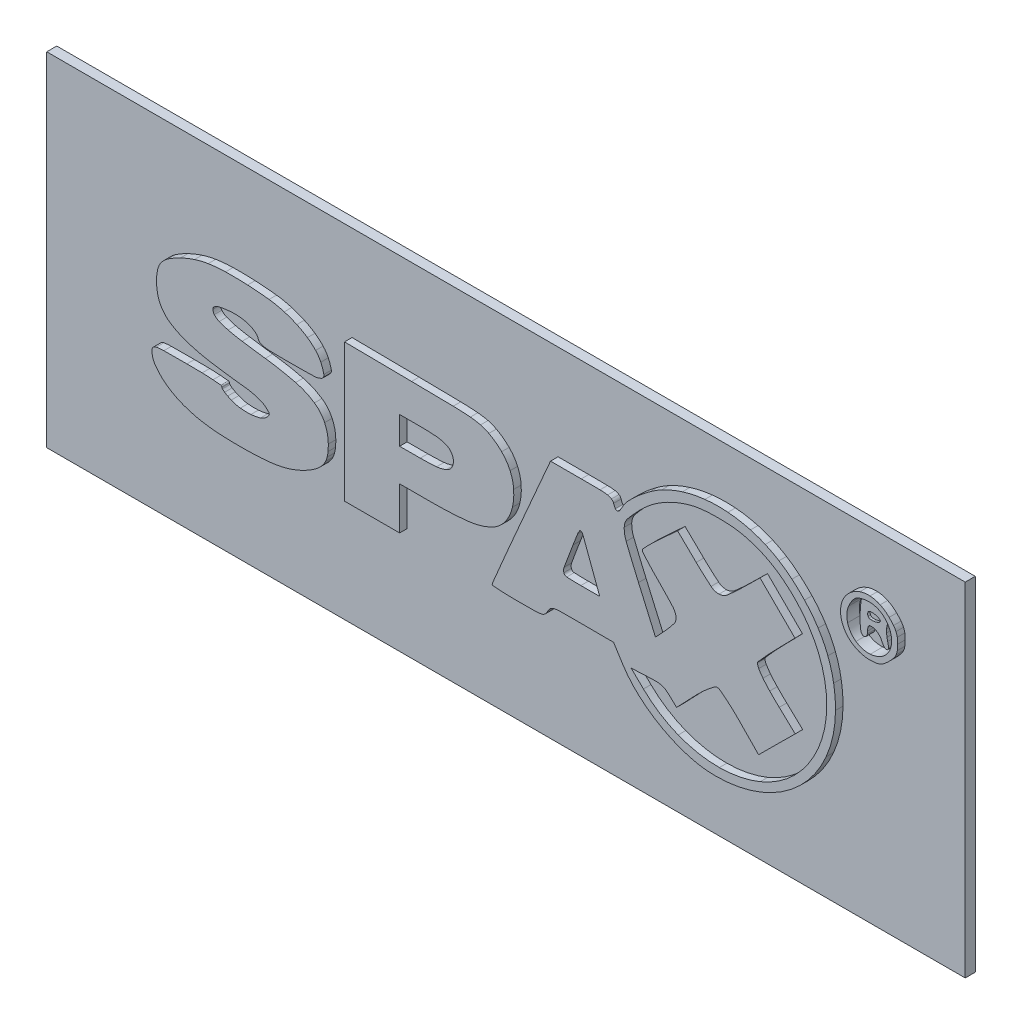
SolidWorks part; units mm, degrees
ref_plane "Front Plane" through (0, 0, 0) normal (0, 0, 1) x (1, 0, 0)
ref_plane "Top Plane" through (0, 0, 0) normal (0, 1, 0) x (1, 0, 0)
ref_plane "Right Plane" through (0, 0, 0) normal (1, 0, 0) x (0, 0, -1)
sketch "Model" plane through (0, 0, 0) normal (0, 0, 1) x (1, 0, 0)
  line L0 (0, 68.5) -> (0, 0)
  line L1 (0, 0) -> (183.5, 0)
  line L2 (183.5, 0) -> (367, 0)
  line L3 (367, 0) -> (367, 68.5)
  line L4 (367, 68.5) -> (367, 137)
  line L5 (367, 137) -> (183.5, 137)
  line L6 (183.5, 137) -> (0, 137)
  line L7 (0, 137) -> (0, 68.5)
  line L8 (233, 43.3516) -> (229.5, 48.9039)
  line L9 (229.5, 48.9039) -> (216.9105, 48.9519)
  line L10 (181.1093, 45.2449) -> (184.4205, 53.0742)
  line L11 (188.1802, 61.882) -> (192.6443, 72.2052)
  line L12 (192.6443, 72.2052) -> (204.2887, 99)
  line L13 (204.2887, 99) -> (216.5769, 99)
  line L14 (157.3185, 61) -> (144, 61)
  line L15 (144, 61) -> (144, 52.5)
  line L16 (144, 52.5) -> (144, 44)
  line L17 (144, 44) -> (133, 44)
  line L18 (133, 44) -> (122, 44)
  line L19 (122, 44) -> (122, 71.5596)
  line L20 (122, 71.5596) -> (122, 99.1193)
  line L21 (122, 99.1193) -> (148.75, 98.8096)
  line L22 (239.4571, 74.5616) -> (246.2264, 59.0751)
  line L23 (246.2264, 59.0751) -> (250.11, 63.2399)
  line L24 (251.2781, 96.8241) -> (255.0562, 100.2835)
  line L25 (255.0562, 100.2835) -> (262.5002, 93.0655)
  line L26 (281.25, 93.8265) -> (288, 100.4464)
  line L27 (288, 100.4464) -> (294.9777, 93.5221)
  line L28 (294.9777, 93.5221) -> (301.9555, 86.5978)
  line L29 (301.9555, 86.5978) -> (294.4777, 78.9138)
  line L30 (295.6641, 59.4982) -> (302.0467, 53.4963)
  line L31 (302.0467, 53.4963) -> (294.7339, 46.2324)
  line L32 (294.7339, 46.2324) -> (287.4212, 38.9684)
  line L33 (287.4212, 38.9684) -> (280.0813, 46.4842)
  line L34 (261.8493, 46.4788) -> (254.6537, 38.9576)
  line L35 (254.6537, 38.9576) -> (251.9685, 41.5302)
  line L36 (242.8916, 43.8014) -> (236.5, 43.5)
  line L37 (236.5, 43.5) -> (241.4223, 38.7189)
  line L38 (216.4075, 62) -> (223.9497, 62)
  line L39 (223.9497, 62) -> (221.0637, 69.75)
  line L40 (221.0637, 69.75) -> (219.89, 72.8972)
  line L41 (219.89, 72.8972) -> (218.7502, 75.9447)
  line L42 (218.7502, 75.9447) -> (217.7735, 78.5484)
  line L43 (217.7735, 78.5484) -> (217.2407, 79.9555)
  line L44 (144, 79.5) -> (144, 74)
  line L45 (144, 74) -> (152.25, 74.0147)
  line L46 (152.25, 84.9853) -> (144, 85)
  line L47 (144, 85) -> (144, 79.5)
  arc A0 (290.0898, 113.0599) -> (284.1892, 115.1571) centre (272.3977, 72.6332) ccw
  arc A1 (295.5669, 110.1672) -> (290.0898, 113.0599) centre (273.152, 74.3567) ccw
  arc A2 (300.7497, 106.3903) -> (295.5669, 110.1672) centre (271.4155, 71.5822) ccw
  arc A3 (305.7714, 101.6482) -> (300.7497, 106.3903) centre (261.3422, 59.629) ccw
  arc A4 (311.219, 94.6965) -> (305.7714, 101.6482) centre (271.165, 68.919) ccw
  arc A5 (315.1092, 87.0501) -> (311.219, 94.6965) centre (275.518, 71.7204) ccw
  arc A6 (317.4144, 78.6997) -> (315.1092, 87.0501) centre (274.6776, 71.395) ccw
  arc A7 (318.1578, 69.6584) -> (317.4144, 78.6997) centre (266.1058, 69.9299) ccw
  arc A8 (314.4227, 51.7702) -> (318.1578, 69.6584) centre (272.309, 69.8976) ccw
  arc A9 (303.9858, 36.6225) -> (314.4227, 51.7702) centre (271.2262, 70.3638) ccw
  arc A10 (288.4274, 26.5204) -> (303.9858, 36.6225) centre (270.5991, 71.0097) ccw
  arc A11 (270.1135, 23.0119) -> (288.4274, 26.5204) centre (270.2393, 71.9074) ccw
  arc A12 (259.627, 24.499) -> (270.1135, 23.0119) centre (270.2123, 61.4243) ccw
  arc A13 (249.0758, 28.8394) -> (259.627, 24.499) centre (273.8083, 73.9683) ccw
  arc A14 (239.7791, 35.376) -> (249.0758, 28.8394) centre (273.6252, 73.6343) ccw
  arc A15 (233, 43.3516) -> (239.7791, 35.376) centre (264.2776, 63.068) ccw
  arc A16 (216.9105, 48.9519) -> (208.649, 48.9371) centre (214.104, -686.3237) ccw
  arc A17 (208.649, 48.9371) -> (205.7901, 48.6731) centre (208.7749, 31.961) ccw
  arc A18 (205.7901, 48.6731) -> (204.2704, 47.9506) centre (206.3507, 45.5345) ccw
  arc A19 (204.2704, 47.9506) -> (203.182, 46.5) centre (207.0283, 44.7475) ccw
  arc A20 (202.1569, 45.0625) -> (203.182, 46.5) centre (198.9709, 48.4187) ccw
  arc A21 (200.7801, 44.3365) -> (202.1569, 45.0625) centre (200.1774, 47.1477) ccw
  arc A22 (198.2741, 44.0515) -> (200.7801, 44.3365) centre (198.0774, 56.9424) ccw
  arc A23 (191.5214, 44) -> (198.2741, 44.0515) centre (191.5213, 486.7578) ccw
  arc A24 (187.4872, 44.0507) -> (191.5214, 44) centre (191.5215, 204.5428) ccw
  arc A25 (184.0907, 44.2071) -> (187.4872, 44.0507) centre (189.5322, 125.3989) ccw
  arc A26 (181.2609, 44.4213) -> (184.0907, 44.2071) centre (195.0833, 208.2248) ccw
  arc A27 (181, 44.7052) -> (181.2609, 44.4213) centre (181.2848, 44.7052) ccw
  arc A28 (181.1093, 45.2449) -> (181, 44.7052) centre (182.3871, 44.7052) ccw
  arc A29 (188.1802, 61.882) -> (184.4205, 53.0742) centre (1701.7504, -589.4075) ccw
  arc A30 (224.0574, 98.9504) -> (216.5769, 99) centre (216.5772, -465.3246) ccw
  arc A31 (227.0962, 98.6964) -> (224.0574, 98.9504) centre (223.7691, 77.198) ccw
  arc A32 (228.6554, 98.1043) -> (227.0962, 98.6964) centre (226.4826, 94.7315) ccw
  arc A33 (229.5, 97) -> (228.6554, 98.1043) centre (227.5441, 96.3792) ccw
  arc A34 (229.5, 97) -> (230.1856, 95.4829) centre (236.2898, 99.155) ccw
  arc A35 (230.1856, 95.4829) -> (230.9729, 95.1226) centre (230.8426, 95.8781) ccw
  arc A36 (230.9729, 95.1226) -> (231.889, 95.7046) centre (230.7333, 96.5116) ccw
  arc A37 (231.889, 95.7046) -> (233.0611, 97.6142) centre (216.3408, 106.5627) ccw
  arc A38 (235.298, 100.6952) -> (233.0611, 97.6142) centre (245.3882, 91.017) ccw
  arc A39 (239.3724, 104.58) -> (235.298, 100.6952) centre (280.8087, 57.0423) ccw
  arc A40 (244.1225, 108.3569) -> (239.3724, 104.58) centre (283.5278, 53.9228) ccw
  arc A41 (248.6856, 111.2333) -> (244.1225, 108.3569) centre (268.7919, 74.2789) ccw
  arc A42 (256.9986, 114.7387) -> (248.6856, 111.2333) centre (270.4447, 71.2412) ccw
  arc A43 (265.9667, 116.6027) -> (256.9986, 114.7387) centre (271.2779, 68.5457) ccw
  arc A44 (275.1724, 116.7474) -> (265.9667, 116.6027) centre (271.3338, 68.0404) ccw
  arc A45 (284.1892, 115.1571) -> (275.1724, 116.7474) centre (271.4171, 69.0968) ccw
  arc A46 (341.3538, 110.6565) -> (339.6, 112.6) centre (321.5322, 94.5323) ccw
  arc A47 (342.3452, 109.0459) -> (341.3538, 110.6565) centre (335.7431, 106.0923) ccw
  arc A48 (342.8416, 107.3117) -> (342.3452, 109.0459) centre (336.5241, 106.4418) ccw
  arc A49 (343, 105) -> (342.8416, 107.3117) centre (326.0537, 105) ccw
  arc A50 (342.8416, 102.6883) -> (343, 105) centre (326.0537, 105) ccw
  arc A51 (342.3452, 100.9541) -> (342.8416, 102.6883) centre (336.5241, 103.5582) ccw
  arc A52 (341.3538, 99.3435) -> (342.3452, 100.9541) centre (335.7431, 103.9077) ccw
  arc A53 (339.6, 97.4) -> (341.3538, 99.3435) centre (321.5322, 115.4677) ccw
  arc A54 (337.6196, 95.6125) -> (339.6, 97.4) centre (321.1442, 115.8558) ccw
  arc A55 (336.0024, 94.6307) -> (337.6196, 95.6125) centre (333.2651, 100.9629) ccw
  arc A56 (334.2232, 94.1496) -> (336.0024, 94.6307) centre (333.4533, 100.5274) ccw
  arc A57 (331.7349, 94) -> (334.2232, 94.1496) centre (331.7348, 114.764) ccw
  arc A58 (325.1323, 95.9651) -> (331.7349, 94) centre (331.7348, 106.0742) ccw
  arc A59 (320.8895, 101.1799) -> (325.1323, 95.9651) centre (331.1722, 105.2127) ccw
  arc A60 (320.5156, 107.7805) -> (320.8895, 101.1799) centre (330.7564, 105.0496) ccw
  arc A61 (324.1107, 113.4397) -> (320.5156, 107.7805) centre (331.2903, 104.9073) ccw
  arc A62 (327.8418, 115.5802) -> (324.1107, 113.4397) centre (331.9031, 104.179) ccw
  arc A63 (331.9489, 116.1759) -> (327.8418, 115.5802) centre (331.3784, 105.6521) ccw
  arc A64 (336.0082, 115.1399) -> (331.9489, 116.1759) centre (331.3658, 105.4204) ccw
  arc A65 (339.6, 112.6) -> (336.0082, 115.1399) centre (330.4016, 103.4016) ccw
  arc A66 (102.9313, 95.5692) -> (97.8951, 97.4576) centre (86.3036, 58.8849) ccw
  arc A67 (107.1665, 93.1697) -> (102.9313, 95.5692) centre (91.7398, 70.8782) ccw
  arc A68 (110.4184, 90.3864) -> (107.1665, 93.1697) centre (95.2683, 75.9768) ccw
  arc A69 (112.506, 87.3462) -> (110.4184, 90.3864) centre (101.9607, 82.3422) ccw
  arc A70 (113.704, 83.7167) -> (112.506, 87.3462) centre (98.5735, 80.7348) ccw
  arc A71 (112.8606, 81.9404) -> (113.704, 83.7167) centre (112.084, 83.3975) ccw
  arc A72 (109.8322, 81.1361) -> (112.8606, 81.9404) centre (109.6297, 88.0023) ccw
  arc A73 (100.5988, 81) -> (109.8322, 81.1361) centre (100.5988, 394.2614) ccw
  arc A74 (93.1747, 81.0507) -> (100.5988, 81) centre (100.5983, 624.6647) ccw
  arc A75 (90.0154, 81.3) -> (93.1747, 81.0507) centre (93.5073, 105.4064) ccw
  arc A76 (88.3759, 81.8579) -> (90.0154, 81.3) centre (90.6934, 85.9807) ccw
  arc A77 (87.5341, 82.8925) -> (88.3759, 81.8579) centre (89.2666, 83.4423) ccw
  arc A78 (87.5341, 82.8925) -> (86.2044, 84.7323) centre (84.0792, 81.7959) ccw
  arc A79 (86.2044, 84.7323) -> (83.5728, 86.0836) centre (80.4813, 76.8247) ccw
  arc A80 (83.5728, 86.0836) -> (80.0127, 86.8047) centre (78.8619, 71.9748) ccw
  arc A81 (80.0127, 86.8047) -> (75.9296, 86.7673) centre (78.1868, 63.2759) ccw
  arc A82 (75.9296, 86.7673) -> (72.1295, 86.2078) centre (79.5782, 48.7959) ccw
  arc A83 (72.1295, 86.2078) -> (70.0148, 85.2994) centre (73.2113, 80.7743) ccw
  arc A84 (70.0148, 85.2994) -> (69.3925, 84.0616) centre (70.8641, 84.097) ccw
  arc A85 (69.3925, 84.0616) -> (69.9589, 82.5496) centre (71.8521, 84.1208) ccw
  arc A86 (69.9589, 82.5496) -> (71.9035, 81.1286) centre (73.7484, 85.6946) ccw
  arc A87 (71.9035, 81.1286) -> (75.4669, 79.9792) centre (81.6577, 105.2693) ccw
  arc A88 (75.4669, 79.9792) -> (81.0643, 78.8705) centre (90.7061, 142.2331) ccw
  arc A89 (81.0643, 78.8705) -> (90.3032, 77.5694) centre (144.2563, 494.1484) ccw
  arc A90 (102.4718, 75.305) -> (90.3032, 77.5694) centre (75.8922, -33.7009) ccw
  arc A91 (109.9567, 71.9867) -> (102.4718, 75.305) centre (96.9985, 52.8587) ccw
  arc A92 (114.0347, 67.1804) -> (109.9567, 71.9867) centre (103.3717, 62.2663) ccw
  arc A93 (115.5, 60.5) -> (114.0347, 67.1804) centre (99.5391, 60.5) ccw
  arc A94 (115.3833, 57.856) -> (115.5, 60.5) centre (85.4829, 60.5) ccw
  arc A95 (115.0209, 55.7289) -> (115.3833, 57.856) centre (102.0271, 59.0371) ccw
  arc A96 (114.3792, 53.9375) -> (115.0209, 55.7289) centre (105.267, 58.2122) ccw
  arc A97 (113.4183, 52.3233) -> (114.3792, 53.9375) centre (105.7194, 58) ccw
  arc A98 (110.499, 49.4275) -> (113.4183, 52.3233) centre (102.6362, 60.2734) ccw
  arc A99 (106.0313, 46.6797) -> (110.499, 49.4275) centre (90.1903, 77.4411) ccw
  arc A100 (100.7815, 44.4384) -> (106.0313, 46.6797) centre (87.8795, 81.9283) ccw
  arc A101 (95.4334, 43.0618) -> (100.7815, 44.4384) centre (89.4697, 77.3076) ccw
  arc A102 (88.9006, 42.3019) -> (95.4334, 43.0618) centre (85.4636, 100.3125) ccw
  arc A103 (80.5831, 42.0451) -> (88.9006, 42.3019) centre (80.2093, 188.9927) ccw
  arc A104 (72.2258, 42.2606) -> (80.5831, 42.0451) centre (80.2074, 189.6343) ccw
  arc A105 (65.5512, 42.9857) -> (72.2258, 42.2606) centre (75.5829, 104.2474) ccw
  arc A106 (57.513, 45.1234) -> (65.5512, 42.9857) centre (72.4473, 85.0984) ccw
  arc A107 (50.9017, 48.6523) -> (57.513, 45.1234) centre (67.4193, 71.6397) ccw
  arc A108 (46.517, 53.0466) -> (50.9017, 48.6523) centre (62.0344, 64.1456) ccw
  arc A109 (45.0037, 57.75) -> (46.517, 53.0466) centre (53.1117, 57.7635) ccw
  arc A110 (45.5133, 59.0287) -> (45.0037, 57.75) centre (46.8553, 57.7531) ccw
  arc A111 (46.8056, 59.7099) -> (45.5133, 59.0287) centre (47.168, 57.4559) ccw
  arc A112 (49.7815, 59.9604) -> (46.8056, 59.7099) centre (49.9517, 40.1398) ccw
  arc A113 (59, 60) -> (49.7815, 59.9604) centre (58.9993, -1013.4316) ccw
  arc A114 (65.0869, 59.9379) -> (59, 60) centre (58.9999, -238.4598) ccw
  arc A115 (69.4199, 59.7312) -> (65.0869, 59.9379) centre (63.4644, -19.5971) ccw
  arc A116 (72.5683, 59.433) -> (69.4199, 59.7312) centre (63.3576, -21.0213) ccw
  arc A117 (73, 58.949) -> (72.5683, 59.433) centre (72.5129, 58.949) ccw
  arc A118 (73, 58.949) -> (73.2209, 58.4484) centre (73.6777, 58.949) ccw
  arc A119 (73.2209, 58.4484) -> (74.0927, 57.7501) centre (79.0768, 64.8664) ccw
  arc A120 (74.0927, 57.7501) -> (75.2951, 57.0157) centre (80.5473, 66.966) ccw
  arc A121 (75.2951, 57.0157) -> (76.7198, 56.3437) centre (83.4781, 72.5185) ccw
  arc A122 (76.7198, 56.3437) -> (80.3686, 55.38) centre (82.0255, 69.0419) ccw
  arc A123 (80.3686, 55.38) -> (84.5795, 55.2908) centre (82.9205, 76.4221) ccw
  arc A124 (84.5795, 55.2908) -> (88.4183, 55.9956) centre (83.0974, 74.1689) ccw
  arc A125 (88.4183, 55.9956) -> (90.8531, 57.4533) centre (86.8354, 61.402) ccw
  arc A126 (90.8531, 57.4533) -> (91.7473, 58.4925) centre (83.4624, 64.7169) ccw
  arc A127 (91.7473, 58.4925) -> (91.9061, 59.1579) centre (91.0612, 59.0079) ccw
  arc A128 (91.9061, 59.1579) -> (91.5437, 59.8313) centre (90.702, 58.9442) ccw
  arc A129 (91.5437, 59.8313) -> (90.2241, 60.9958) centre (74.7475, 42.1272) ccw
  arc A130 (90.2241, 60.9958) -> (88.9404, 61.7792) centre (86.7833, 56.8009) ccw
  arc A131 (88.9404, 61.7792) -> (86.9676, 62.513) centre (81.0055, 43.4662) ccw
  arc A132 (86.9676, 62.513) -> (84.6442, 63.1156) centre (79.7365, 39.4125) ccw
  arc A133 (84.6442, 63.1156) -> (82.2241, 63.5) centre (79.3148, 37.3753) ccw
  arc A134 (68.0488, 65.4507) -> (82.2241, 63.5) centre (112.866, 338.6551) ccw
  arc A135 (58.7008, 67.7686) -> (68.0488, 65.4507) centre (77.7467, 124.5688) ccw
  arc A136 (52.5242, 70.745) -> (58.7008, 67.7686) centre (67.407, 93.7328) ccw
  arc A137 (48.7178, 74.7351) -> (52.5242, 70.745) centre (58.9761, 80.7106) ccw
  arc A138 (47.3215, 78.312) -> (48.7178, 74.7351) centre (59.4435, 80.9829) ccw
  arc A139 (46.8506, 82.629) -> (47.3215, 78.312) centre (66.9532, 82.6375) ccw
  arc A140 (47.3124, 86.7954) -> (46.8506, 82.629) centre (65.804, 82.6371) ccw
  arc A141 (48.7113, 89.8999) -> (47.3124, 86.7954) centre (55.5851, 84.9351) ccw
  arc A142 (51.5372, 92.6042) -> (48.7113, 89.8999) centre (57.4777, 83.5681) ccw
  arc A143 (56.3795, 95.3461) -> (51.5372, 92.6042) centre (74.5882, 57.5413) ccw
  arc A144 (62.0239, 97.626) -> (56.3795, 95.3461) centre (76.7247, 53.1053) ccw
  arc A145 (67.504, 98.9514) -> (62.0239, 97.626) centre (72.863, 64.8004) ccw
  arc A146 (74.4362, 99.5586) -> (67.504, 98.9514) centre (75.4102, 48.5691) ccw
  arc A147 (83.2454, 99.4264) -> (74.4362, 99.5586) centre (76.9035, -29.5997) ccw
  arc A148 (91.8298, 98.7138) -> (83.2454, 99.4264) centre (76.9721, -28.2064) ccw
  arc A149 (97.8951, 97.4576) -> (91.8298, 98.7138) centre (87.7185, 63.5931) ccw
  arc A150 (184.7719, 92.4885) -> (179.6555, 96.2779) centre (169.3666, 77.0371) ccw
  arc A151 (188.1378, 87.625) -> (184.7719, 92.4885) centre (173.2042, 80.8862) ccw
  arc A152 (189.5735, 81.8526) -> (188.1378, 87.625) centre (173.0057, 80.7967) ccw
  arc A153 (189.0689, 75.4172) -> (189.5735, 81.8526) centre (166.7984, 80.4011) ccw
  arc A154 (185.9002, 68.6231) -> (189.0689, 75.4172) centre (172.0201, 79.2325) ccw
  arc A155 (180.2945, 64.1618) -> (185.9002, 68.6231) centre (174.2119, 77.5572) ccw
  arc A156 (171.2751, 61.7184) -> (180.2945, 64.1618) centre (168.295, 90.5879) ccw
  arc A157 (157.3185, 61) -> (171.2751, 61.7184) centre (157.3185, 196.923) ccw
  arc A158 (165.4126, 98.5655) -> (148.75, 98.8096) centre (117.3988, -2609.7852) ccw
  arc A159 (172.2522, 98.2251) -> (165.4126, 98.5655) centre (163.516, -8.4198) ccw
  arc A160 (176.326, 97.5578) -> (172.2522, 98.2251) centre (170.1595, 72.6793) ccw
  arc A161 (179.6555, 96.2779) -> (176.326, 97.5578) centre (172.858, 83.5663) ccw
  arc A162 (260, 111.64) -> (254.5651, 109.7858) centre (271.9828, 67.6231) ccw
  arc A163 (254.5651, 109.7858) -> (249.466, 107.28) centre (271.2587, 69.376) ccw
  arc A164 (249.466, 107.28) -> (244.772, 104.1552) centre (270.9264, 69.954) ccw
  arc A165 (244.772, 104.1552) -> (240.5453, 100.4546) centre (270.5359, 70.4647) ccw
  arc A166 (240.5453, 100.4546) -> (235.1414, 94.5045) centre (299.6998, 41.3014) ccw
  arc A167 (235.1414, 94.5045) -> (233.741, 90.8466) centre (239.8939, 90.588) ccw
  arc A168 (233.741, 90.8466) -> (234.5117, 86.3564) centre (244.5582, 90.392) ccw
  arc A169 (234.5117, 86.3564) -> (239.4571, 74.5616) centre (628.6071, 244.6617) ccw
  arc A170 (250.11, 63.2399) -> (253.7432, 67.6016) centre (212.9845, 97.8589) ccw
  arc A171 (253.7432, 67.6016) -> (254.4255, 70.2346) centre (250.836, 69.7598) ccw
  arc A172 (254.4255, 70.2346) -> (253.1694, 72.9902) centre (249.2824, 69.5543) ccw
  arc A173 (253.1694, 72.9902) -> (248.1055, 78.3937) centre (157.7931, -11.3158) ccw
  arc A174 (245.3824, 81.1949) -> (248.1055, 78.3937) centre (376.7381, 206.1681) ccw
  arc A175 (243.0873, 83.6882) -> (245.3824, 81.1949) centre (319.966, 152.1547) ccw
  arc A176 (241.1971, 85.8427) -> (243.0873, 83.6882) centre (386.5045, 211.4129) ccw
  arc A177 (241, 86.3723) -> (241.1971, 85.8427) centre (241.81, 86.3723) ccw
  arc A178 (241.3206, 87.2096) -> (241, 86.3723) centre (242.2536, 86.3723) ccw
  arc A179 (243.1785, 89.1871) -> (241.3206, 87.2096) centre (285.6064, 47.4642) ccw
  arc A180 (246.1422, 92.0751) -> (243.1785, 89.1871) centre (312.4073, 21.1086) ccw
  arc A181 (251.2781, 96.8241) -> (246.1422, 92.0751) centre (735.4848, -431.9856) ccw
  arc A182 (262.5002, 93.0655) -> (268.4422, 87.7388) centre (333.4809, 166.2683) ccw
  arc A183 (268.4422, 87.7388) -> (271.6252, 86.6643) centre (271.435, 91.3524) ccw
  arc A184 (271.6252, 86.6643) -> (274.8565, 87.9416) centre (271.4115, 91.9308) ccw
  arc A185 (274.8565, 87.9416) -> (281.25, 93.8265) centre (185.1848, 191.7793) ccw
  arc A186 (294.4777, 78.9138) -> (291.6116, 75.9194) centre (473.994, -95.7816) ccw
  arc A187 (291.6116, 75.9194) -> (289.1966, 73.287) centre (392.5576, -19.1144) ccw
  arc A188 (289.1966, 73.287) -> (287.1686, 70.9968) centre (532.122, -143.8807) ccw
  arc A189 (287.1686, 70.9968) -> (287, 70.5491) centre (287.679, 70.5491) ccw
  arc A190 (287, 70.5491) -> (287.4762, 68.8137) centre (290.4002, 70.5491) ccw
  arc A191 (287.4762, 68.8137) -> (289.1784, 66.3271) centre (307.5312, 80.716) ccw
  arc A192 (289.1784, 66.3271) -> (291.8634, 63.2459) centre (320.1838, 90.6358) ccw
  arc A193 (291.8634, 63.2459) -> (295.6641, 59.4982) centre (372.7583, 141.4829) ccw
  arc A194 (280.0813, 46.4842) -> (277.1351, 49.3632) centre (217.0641, -15.0584) ccw
  arc A195 (277.1351, 49.3632) -> (274.3546, 51.7922) centre (238.3035, 7.7193) ccw
  arc A196 (274.3546, 51.7922) -> (271.9642, 53.6482) centre (236.6625, 5.7132) ccw
  arc A197 (271.9642, 53.6482) -> (270.8931, 54) centre (270.8931, 52.1939) ccw
  arc A198 (270.8931, 54) -> (269.8271, 53.6458) centre (270.8931, 52.2186) ccw
  arc A199 (269.8271, 53.6458) -> (267.4741, 51.7907) centre (304.1998, 7.6297) ccw
  arc A200 (267.4741, 51.7907) -> (264.7402, 49.3598) centre (302.8678, 9.2315) ccw
  arc A201 (264.7402, 49.3598) -> (261.8493, 46.4788) centre (323.7098, -12.704) ccw
  arc A202 (251.9685, 41.5302) -> (250.2416, 42.928) centre (242.7554, 31.9139) ccw
  arc A203 (250.2416, 42.928) -> (248.6738, 43.6302) centre (247.4823, 38.8684) ccw
  arc A204 (248.6738, 43.6302) -> (246.6101, 43.8861) centre (246.5966, 35.3288) ccw
  arc A205 (246.6101, 43.8861) -> (242.8916, 43.8014) centre (246.4903, -32.5172) ccw
  arc A206 (241.4223, 38.7189) -> (255.3049, 29.7568) centre (270.7443, 68.9065) ccw
  arc A207 (255.3049, 29.7568) -> (271.7319, 26.6943) centre (271.4237, 70.6292) ccw
  arc A208 (271.7319, 26.6943) -> (288.1109, 29.9871) centre (271.4239, 70.6098) ccw
  arc A209 (288.1109, 29.9871) -> (301.8571, 39.1429) centre (272.1446, 68.8554) ccw
  arc A210 (301.8571, 39.1429) -> (311.3088, 53.1959) centre (270.6903, 70.3097) ccw
  arc A211 (311.3088, 53.1959) -> (314.6575, 69.6538) centre (271.9733, 69.7691) ccw
  arc A212 (314.6575, 69.6538) -> (311.3962, 86.1008) centre (272.1339, 69.7687) ccw
  arc A213 (311.3962, 86.1008) -> (302.0218, 100.1252) centre (271.2101, 69.3844) ccw
  arc A214 (302.0218, 100.1252) -> (297.4541, 104.2358) centre (261.5605, 59.7571) ccw
  arc A215 (297.4541, 104.2358) -> (292.8962, 107.3941) centre (273.5877, 74.661) ccw
  arc A216 (292.8962, 107.3941) -> (288.0202, 109.7982) centre (274.4298, 76.0885) ccw
  arc A217 (288.0202, 109.7982) -> (282.5, 111.6406) centre (270.2022, 65.6026) ccw
  arc A218 (282.5, 111.6406) -> (277.3836, 112.5684) centre (274.2725, 80.8403) ccw
  arc A219 (277.3836, 112.5684) -> (271.2073, 112.8704) centre (271.2092, 49.5992) ccw
  arc A220 (271.2073, 112.8704) -> (265.0508, 112.5687) centre (271.2093, 49.8663) ccw
  arc A221 (265.0508, 112.5687) -> (260, 111.64) centre (268.0444, 82.0903) ccw
  arc A222 (213.2679, 74.4555) -> (209.7135, 64.9816) centre (1053.4587, -246.1708) ccw
  arc A223 (209.7135, 64.9816) -> (209.6123, 63.081) centre (212.7337, 63.8678) ccw
  arc A224 (209.6123, 63.081) -> (210.7458, 62.1489) centre (210.8107, 63.3831) ccw
  arc A225 (210.7458, 62.1489) -> (216.4075, 62) centre (216.4074, 169.7005) ccw
  arc A226 (217.2407, 79.9555) -> (216.604, 80.8394) centre (215.259, 79.1993) ccw
  arc A227 (216.604, 80.8394) -> (215.9704, 80.7571) centre (216.3259, 80.5003) ccw
  arc A228 (215.9704, 80.7571) -> (215.1353, 79.2383) centre (221.7045, 76.6152) ccw
  arc A229 (215.1353, 79.2383) -> (213.2679, 74.4555) centre (525.9043, -44.8506) ccw
  arc A230 (326.6563, 112.8675) -> (325.8493, 112.2209) centre (328.4077, 109.8546) ccw
  arc A231 (325.8493, 112.2209) -> (324.9371, 111.1124) centre (334.9591, 103.7951) ccw
  arc A232 (324.9371, 111.1124) -> (324.072, 109.7773) centre (336.472, 102.6904) ccw
  arc A233 (324.072, 109.7773) -> (323.3929, 108.3979) centre (334.8932, 103.5927) ccw
  arc A234 (323.3929, 108.3979) -> (322.9904, 102.4281) centre (331.9501, 104.8224) ccw
  arc A235 (322.9904, 102.4281) -> (326.3417, 97.6371) centre (331.2437, 104.6337) ccw
  arc A236 (326.3417, 97.6371) -> (332.0482, 96.0672) centre (331.395, 104.8496) ccw
  arc A237 (332.0482, 96.0672) -> (337.6715, 98.3939) centre (331.3265, 105.7703) ccw
  arc A238 (337.6715, 98.3939) -> (340.3573, 102.8461) centre (332.243, 104.7049) ccw
  arc A239 (340.3573, 102.8461) -> (339.9807, 108.1703) centre (331.4336, 104.8903) ccw
  arc A240 (339.9807, 108.1703) -> (336.6927, 112.404) centre (331.3425, 104.8553) ccw
  arc A241 (336.6927, 112.404) -> (331.6942, 113.9696) centre (331.7752, 105.4658) ccw
  arc A242 (331.6942, 113.9696) -> (330.3361, 113.8793) centre (331.8083, 101.9912) ccw
  arc A243 (330.3361, 113.8793) -> (328.8967, 113.6333) centre (332.284, 98.1499) ccw
  arc A244 (328.8967, 113.6333) -> (327.5878, 113.2814) centre (331.9638, 99.6133) ccw
  arc A245 (327.5878, 113.2814) -> (326.6563, 112.8675) centre (329.0249, 108.7926) ccw
  arc A246 (336.2355, 109.9204) -> (335.4646, 110.6495) centre (332.9756, 107.2457) ccw
  arc A247 (336.7074, 109.0888) -> (336.2355, 109.9204) centre (334.0644, 108.139) ccw
  arc A248 (336.8715, 108.1501) -> (336.7074, 109.0888) centre (334.085, 108.1464) ccw
  arc A249 (336.738, 107.1061) -> (336.8715, 108.1501) centre (332.7665, 108.1447) ccw
  arc A250 (336.738, 107.1061) -> (336.5777, 106.0552) centre (341.6707, 105.8162) ccw
  arc A251 (336.5777, 106.0552) -> (336.5821, 104.6888) centre (350.2115, 105.4152) ccw
  arc A252 (336.5821, 104.6888) -> (336.7298, 103.2492) centre (351.3309, 105.4749) ccw
  arc A253 (336.7298, 103.2492) -> (337.0125, 101.9566) centre (346.9537, 104.8077) ccw
  arc A254 (337.3468, 99.8251) -> (337.0125, 101.9566) centre (328.6084, 99.5463) ccw
  arc A255 (336.7072, 98.9534) -> (337.3468, 99.8251) centre (336.4711, 99.7971) ccw
  arc A256 (335.6133, 99.3239) -> (336.7072, 98.9534) centre (336.4314, 99.9391) ccw
  arc A257 (334.4871, 101.25) -> (335.6133, 99.3239) centre (343.3397, 105.1338) ccw
  arc A258 (334.4871, 101.25) -> (333.9428, 102.1344) centre (331.0365, 99.7361) ccw
  arc A259 (333.9428, 102.1344) -> (333.129, 102.9329) centre (329.7465, 98.6717) ccw
  arc A260 (333.129, 102.9329) -> (332.1838, 103.5313) centre (329.8601, 98.8147) ccw
  arc A261 (332.1838, 103.5313) -> (331.25, 103.8196) centre (330.8143, 100.7514) ccw
  arc A262 (331.25, 103.8196) -> (330.0911, 103.8691) centre (330.4196, 97.9726) ccw
  arc A263 (330.0911, 103.8691) -> (329.4378, 103.5769) centre (330.1469, 102.8678) ccw
  arc A264 (329.4378, 103.5769) -> (329.0952, 102.8931) centre (330.2951, 102.7196) ccw
  arc A265 (329.0952, 102.8931) -> (329, 101.5696) centre (338.2499, 101.5696) ccw
  arc A266 (328.9029, 100.4877) -> (329, 101.5696) centre (322.9236, 101.5695) ccw
  arc A267 (328.6041, 99.6783) -> (328.9029, 100.4877) centre (326.4605, 100.9296) ccw
  arc A268 (328.1247, 99.1812) -> (328.6041, 99.6783) centre (327.3439, 100.4139) ccw
  arc A269 (327.5, 99) -> (328.1247, 99.1812) centre (327.5, 100.1674) ccw
  arc A270 (326.7794, 99.3308) -> (327.5, 99) centre (327.5, 99.9503) ccw
  arc A271 (326.3143, 100.2222) -> (326.7794, 99.3308) centre (328.4573, 100.7733) ccw
  arc A272 (326.0651, 101.8934) -> (326.3143, 100.2222) centre (334.2192, 102.2549) ccw
  arc A273 (326, 104.8333) -> (326.0651, 101.8934) centre (392.3815, 104.8333) ccw
  arc A274 (326.0485, 107.1165) -> (326, 104.8333) centre (379.7391, 104.8334) ccw
  arc A275 (326.1958, 109.149) -> (326.0485, 107.1165) centre (360.1527, 105.6662) ccw
  arc A276 (326.4037, 110.8105) -> (326.1958, 109.149) centre (363.6527, 105.3072) ccw
  arc A277 (326.6667, 111.3333) -> (326.4037, 110.8105) centre (327.3258, 110.6742) ccw
  arc A278 (328.0494, 111.9638) -> (326.6667, 111.3333) centre (328.2018, 109.7982) ccw
  arc A279 (330.7824, 111.9538) -> (328.0494, 111.9638) centre (329.3482, 93.4998) ccw
  arc A280 (333.5974, 111.5118) -> (330.7824, 111.9538) centre (329.3686, 93.7634) ccw
  arc A281 (335.4646, 110.6495) -> (333.5974, 111.5118) centre (332.3902, 106.445) ccw
  arc A282 (152.25, 74.0147) -> (158.7628, 74.2818) centre (152.1014, 157.1795) ccw
  arc A283 (158.7628, 74.2818) -> (162.6347, 75.2144) centre (157.7372, 87.0446) ccw
  arc A284 (162.6347, 75.2144) -> (164.7177, 76.9229) centre (160.8593, 79.503) ccw
  arc A285 (164.7177, 76.9229) -> (164.7177, 82.0771) centre (160.8637, 79.5) ccw
  arc A286 (164.7177, 82.0771) -> (162.6347, 83.7856) centre (160.8593, 79.497) ccw
  arc A287 (162.6347, 83.7856) -> (158.7628, 84.7182) centre (157.7372, 71.9554) ccw
  arc A288 (158.7628, 84.7182) -> (152.25, 84.9853) centre (152.1014, 1.8205) ccw
  arc A289 (329, 107.5) -> (329.1563, 106.7775) centre (330.7484, 107.5) ccw
  arc A290 (329.1563, 106.7775) -> (329.5891, 106.3208) centre (330.0337, 107.1756) ccw
  arc A291 (329.5891, 106.3208) -> (330.3544, 106.1242) centre (330.3954, 107.8711) ccw
  arc A292 (330.3544, 106.1242) -> (331.5311, 106.1836) centre (330.5415, 114.0992) ccw
  arc A293 (331.5311, 106.1836) -> (332.5002, 106.378) centre (330.6979, 112.8482) ccw
  arc A294 (332.5002, 106.378) -> (333.3187, 106.7008) centre (331.3627, 110.4615) ccw
  arc A295 (333.3187, 106.7008) -> (333.8825, 107.0937) centre (332.0871, 109.0688) ccw
  arc A296 (333.8825, 107.0937) -> (333.8825, 107.9063) centre (333.5132, 107.5) ccw
  arc A297 (333.8825, 107.9063) -> (333.3187, 108.2992) centre (332.0871, 105.9312) ccw
  arc A298 (333.3187, 108.2992) -> (332.5002, 108.622) centre (331.3627, 104.5385) ccw
  arc A299 (332.5002, 108.622) -> (331.5311, 108.8164) centre (330.6979, 102.1518) ccw
  arc A300 (331.5311, 108.8164) -> (330.3544, 108.8758) centre (330.5415, 100.9008) ccw
  arc A301 (330.3544, 108.8758) -> (329.5891, 108.6792) centre (330.3954, 107.1289) ccw
  arc A302 (329.5891, 108.6792) -> (329.1563, 108.2225) centre (330.0337, 107.8244) ccw
  arc A303 (329.1563, 108.2225) -> (329, 107.5) centre (330.7484, 107.5) ccw
  point P655 (0, 0)
extrude "Saliente-Extruir1" add sketch "Model" along normal blind 4 contours L6 L7 L0 L1 L2 L3 L4 L5 A161 A150 A151 A152 A153 A154 A155 A156 A157 L14 L15 L16 L17 L18 L19 L20 L21 A158 A159 A160 A149 A66 A67 A68 A69 A70 A71 A72 A73 A74 A75 A76 A77 A78 A79 A80 A81 A82 A83 A84 A85 | A287 A288 L46 L47 L44 L45 A282 A283 A284 A285 A286 | A228 A229 A222 A223 A224 A225 L38 L39 L40 L41 L42 L43 A226 A227 | A220 A221 A162 A163 A164 A165 A166 A167 A168 A169 L22 L23 A170 A171 A172 A173 A174 A175 A176 A177 A178 A179 A180 A181 L24 L25 A182 A183 A184 A185 L26 L27 L28 L29 A186 A187 A188 A189 A190 A191 A192 A193 L30 L31 L32 L33 A194 A195 A196 A197 A198 | A302 A303 A289 A290 A291 A292 A293 A294 A295 A296 A297 A298 A299 A300 A301 region at (3.9174, 102.75, 0) region at (238.0302, 80.8975, 0) region at (216.3648, 68.8031, 0) region at (153.9786, 79.5, 0) region at (331.3255, 107.5, 0)
extrude "Saliente-Extruir2" add sketch "Model<3>" along normal blind 7 separate body contours A0 A45 A44 A43 A42 A41 A40 A39 A38 A37 A36 A35 A34 A33 A32 A31 A30 L13 L12 L11 A29 L10 A28 A27 A26 A25 A24 A23 A22 A21 A20 A19 A18 A17 A16 L9 L8 A15 A14 A13 A12 A11 A10 A9 A8 A7 A6 A5 A4 A3 A2 | A150 A161 A160 A159 A158 L21 L20 L19 L18 L17 L16 L15 L14 A157 A156 A155 A154 A153 A152 A151 A288 A287 A286 A285 A284 A283 A282 L45 L44 L47 L46 | A66 A149 A148 A147 A146 A145 A144 A143 A142 A141 A140 A139 A138 A137 A136 A135 A134 A133 A132 A131 A130 A129 A128 A127 A126 A125 A124 A123 A122 A121 A120 A119 A118 A117 A116 A115 A114 A113 A112 A111 A110 A109 A108 A107 A106 A105 A104 A103 A102 A101 A100 | A46 A65 A64 A63 A62 A61 A60 A59 A58 A57 A56 A55 A54 A53 A52 A51 A50 A49 A48 A47 A245 A244 A243 A242 A241 A240 A239 A238 A237 A236 A235 A234 A233 A232 A231 A230 region at (232.6561, 47.0141, 0) region at (150.6592, 61.8724, 0) region at (341.6312, 109.7168, 0) region at (80.7286, 70.4768, 0)
sketch "Model<3>" plane through (0, 0, 0) normal (0, 0, 1) x (1, 0, 0) same geometry as "Model"
extrude "Saliente-Extruir3" add sketch "Model<4>" along normal blind 2 contours A244 A245 A230 A231 A232 A233 A234 A235 A236 A237 A238 A239 A240 A241 A242 A243 A281 A246 A247 A248 A249 A250 A251 A252 A253 A254 A255 A256 A257 A258 A259 A260 A261 A262 A263 A264 A265 A266 A267 A268 A269 A270 A271 A272 A273 A274 A275 A276 A277 A278 region at (327.2137, 112.8681, 0)
sketch "Model<4>" plane through (0, 0, 0) normal (0, 0, 1) x (1, 0, 0) same geometry as "Model"
extrude "Saliente-Extruir4" add sketch "Model<5>" along normal blind 5 contours A246 A281 A280 A279 A278 A277 A276 A275 A274 A273 A272 A271 A270 A269 A268 A267 A266 A265 A264 A263 A262 A261 A260 A259 A258 A257 A256 A255 A254 A253 A252 A251 A250 A249 A248 A247 A303 A302 A301 A300 A299 A298 A297 A296 A295 A294 A293 A292 A291 A290 region at (331.3378, 106.0469, 0)
sketch "Model<5>" plane through (0, 0, 0) normal (0, 0, 1) x (1, 0, 0) same geometry as "Model"
